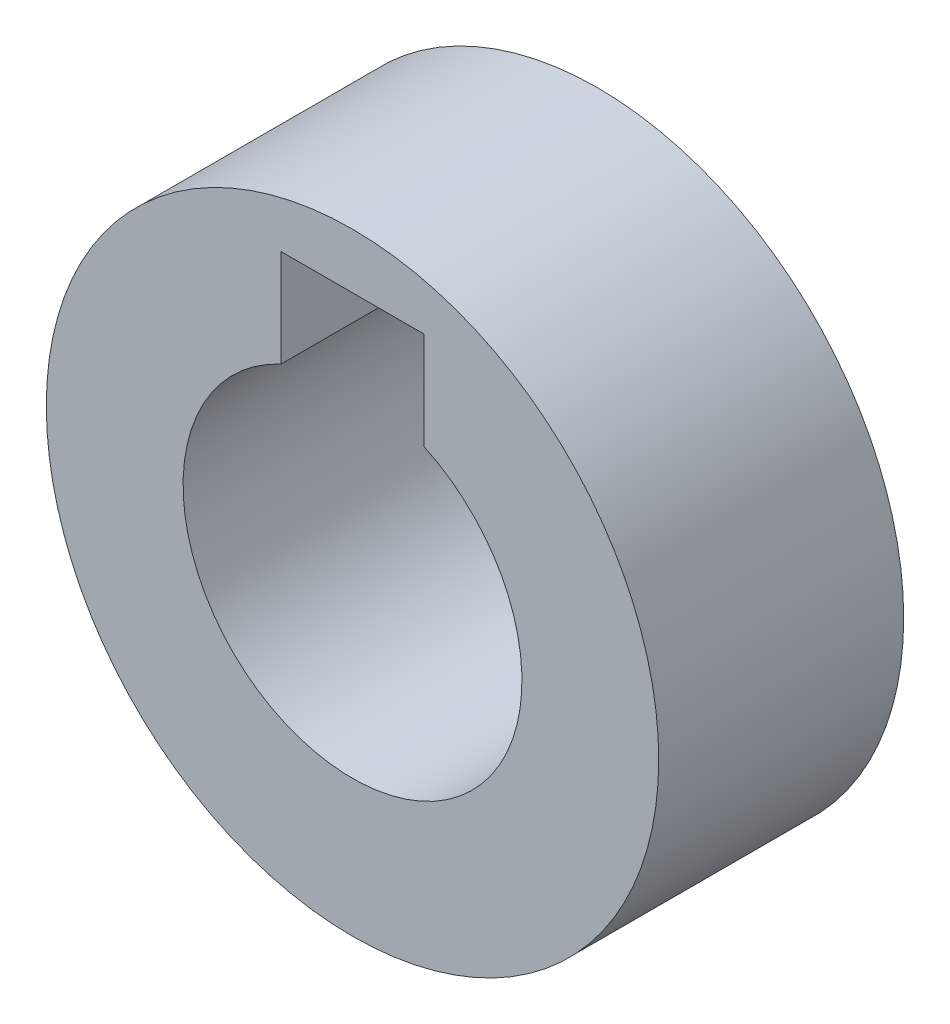
SolidWorks part; units mm, degrees
ref_plane "Ebene vorne" through (0, 0, 0) normal (0, 0, 1) x (1, 0, 0)
ref_plane "Ebene oben" through (0, 0, 0) normal (0, 1, 0) x (1, 0, 0)
ref_plane "Ebene rechts" through (0, 0, 0) normal (1, 0, 0) x (0, 0, -1)
sketch "Skizze1" plane through (0, 0, 0) normal (0, 0, 1) x (1, 0, 0)
  line L1 (-1.75, 2.15) -> (1.75, 2.15)
  line L2 (-1.75, 2.15) -> (-1.75, 6.15)
  line L3 (-1.75, 6.15) -> (1.75, 6.15)
  line L4 (1.75, 2.15) -> (1.75, 6.15)
  line L5 (-1.75, 2.15) -> (1.75, 6.15) construction
  line L6 (-1.75, 6.15) -> (1.75, 2.15) construction
  circle A0 centre (0, 0) radius 4.15
  circle A1 centre (0, 0) radius 7.5
  point P4 (0, 4.15)
  dimension "D1" = 8.3
  dimension "D2" = 15
  dimension "D3" = 3.5
  dimension "D4" = 4
extrude "Aufsatz-Linear austragen1" add sketch "Skizze1" along normal blind 6 contours A1 A0 L2 L3 L4 region at (-7.2879, 0, 0)
